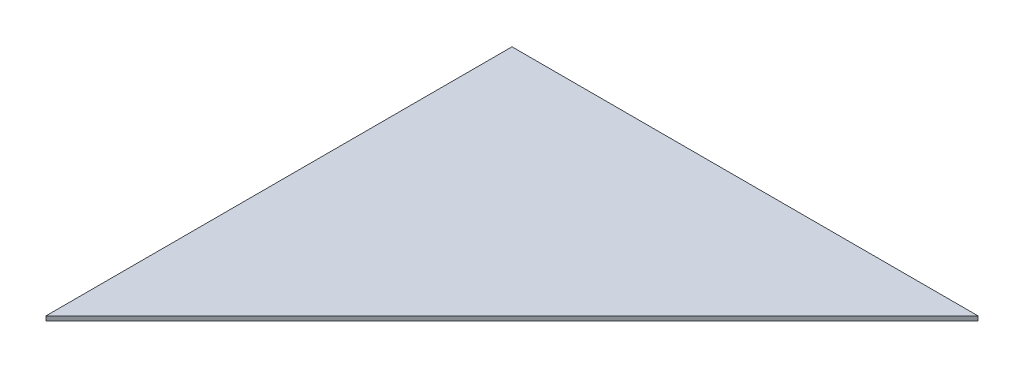
SolidWorks part; units mm, degrees
material "Teak"
ref_plane "Front Plane" through (0, 0, 0) normal (0, 0, 1) x (1, 0, 0)
ref_plane "Top Plane" through (0, 0, 0) normal (0, 1, 0) x (1, 0, 0)
ref_plane "Right Plane" through (0, 0, 0) normal (1, 0, 0) x (0, 0, -1)
sketch "Sketch1" plane through (0, 0, 0) normal (0, 1, 0) x (1, 0, 0)
  line L1 (-609.6, -609.6) -> (609.6, -609.6)
  line L2 (-609.6, -609.6) -> (-609.6, 609.6)
  line L3 (-609.6, 609.6) -> (609.6, 609.6)
  line L4 (609.6, -609.6) -> (609.6, 609.6)
  line L5 (-609.6, -609.6) -> (609.6, 609.6) construction
  line L6 (-609.6, 609.6) -> (609.6, -609.6) construction
  point P0 (0, 0)
  dimension "D1" = 1219.2
extrude "Boss-Extrude1" add sketch "Sketch1" along normal blind 5.5562
sketch "Sketch2" plane through (0, 0, 0) normal (0, -1, 0) x (1, 0, 0)
  line L1 (-52.8241, -609.6) -> (-609.6, -52.8241)
  line L4 (-609.6, -52.8241) -> (-609.6, -609.6)
  line L5 (-609.6, 609.6) -> (609.6, 609.6)
  line L6 (609.6, 609.6) -> (609.6, -609.6)
  line L7 (609.6, -609.6) -> (-52.8241, -609.6)
  line L8 (-609.6, -52.8241) -> (-609.6, 609.6)
  line L9 (-609.6, -609.6) -> (-52.8241, -609.6)
  line M1 (609.6, -609.6) -> (609.6, 609.6)
  line M2 (609.6, 609.6) -> (-609.6, 609.6)
  line M3 (-609.6, 609.6) -> (-609.6, -609.6)
  line M4 (-609.6, -609.6) -> (609.6, -609.6)
extrude "Cut-Extrude1" cut sketch "Sketch2" against normal through all contours L1 M4 M1 M2 M3 region at (49.3606, 0, 49.3606)
